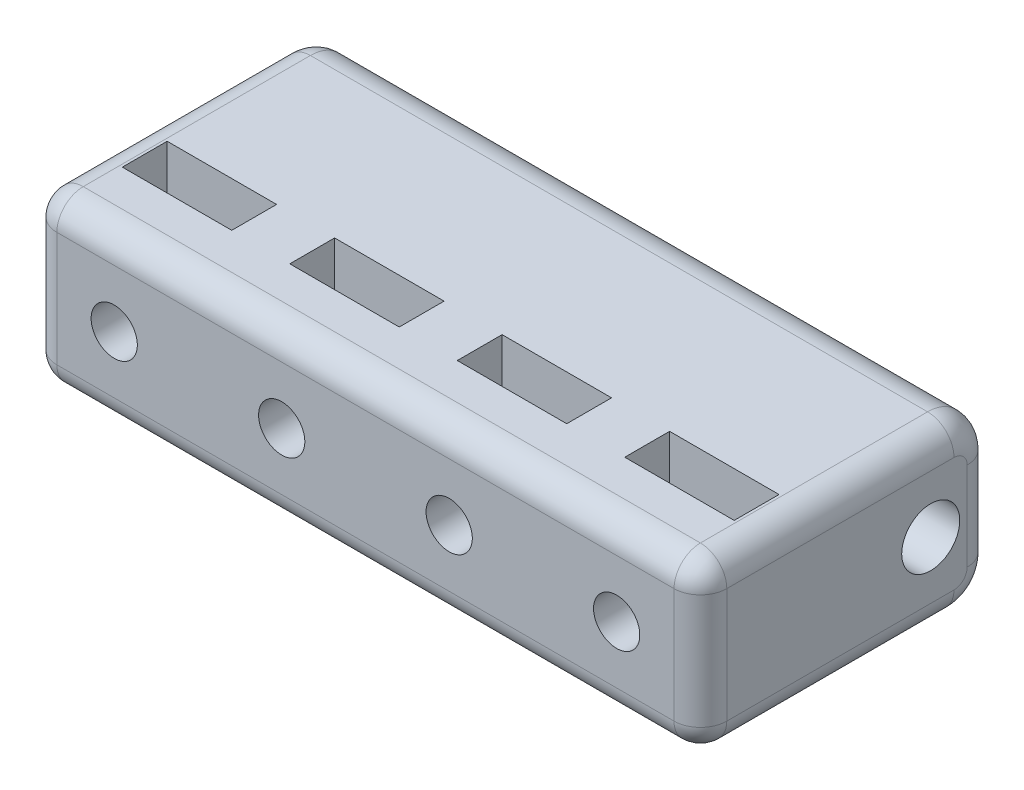
SolidWorks part; units mm, degrees
ref_plane "Front Plane" through (0, 0, 0) normal (0, 0, 1) x (1, 0, 0)
ref_plane "Top Plane" through (0, 0, 0) normal (0, 1, 0) x (1, 0, 0)
ref_plane "Right Plane" through (0, 0, 0) normal (1, 0, 0) x (0, 0, -1)
sketch "Sketch1" plane through (0, 0, 0) normal (0, 1, 0) x (1, 0, 0)
  line L1 (0, 0) -> (-50.8, 0)
  line L2 (0, 0) -> (0, -22.225)
  line L3 (0, -22.225) -> (-50.8, -22.225)
  line L4 (-50.8, 0) -> (-50.8, -22.225)
  dimension "D1" = 22.225
  dimension "D2" = 50.8
extrude "Boss-Extrude1" add sketch "Sketch1" along normal blind 12.7
sketch "Sketch2" plane through (-50.8, 0, 0) normal (-1, 0, 0) x (0, 0, 1)
  line L0 (0, 12.7) -> (0, 0) construction
  circle A0 centre (4.7625, 6.35) radius 2.2
  point P9 (0, 6.35)
  dimension "D1" = 4.4
  dimension "D2" = 4.7625
extrude "Cut-Extrude1" cut sketch "Sketch2" against normal through all
sketch "Sketch3" plane through (0, 12.7, 0) normal (0, 1, 0) x (1, 0, 0)
  line L0 (-50.8, -17.4625) -> (0, -17.4625) construction
  line L1 (-50.8, 0) -> (-50.8, -22.225) construction
  line L2 (0, -22.225) -> (0, 0) construction
  dimension "D1" = 17.4625
ref_plane "Plane1" through (0, 0, 17.4625) normal (0, 0, 1) x (1, 0, 0)
sketch "Sketch4" plane through (0, 0, 17.4625) normal (0, 0, 1) x (1, 0, 0)
  line L0 (-50.8, 12.7) -> (-50.8, 0) construction
  line L1 (-44.45, 1.558) -> (-40.3, 3.954)
  line L2 (-40.3, 3.954) -> (-40.3, 8.746)
  line L3 (-40.3, 8.746) -> (-44.45, 11.142)
  line L4 (-44.45, 11.142) -> (-48.6, 8.746)
  line L5 (-48.6, 8.746) -> (-48.6, 3.954)
  line L6 (-48.6, 3.954) -> (-44.45, 1.558)
  line L7 (-48.6, 8.746) -> (-48.6, 12.7)
  line L26 (-50.8, 12.7) -> (0, 12.7) construction
  line L27 (-48.6, 12.7) -> (-40.3, 12.7)
  line L28 (-40.3, 12.7) -> (-40.3, 8.746)
  line L29 (-35.9, 8.746) -> (-35.9, 12.7)
  line L30 (-35.9, 8.746) -> (-35.9, 3.954)
  line L31 (-35.9, 3.954) -> (-31.75, 1.558)
  line L32 (-31.75, 1.558) -> (-27.6, 3.954)
  line L33 (-27.6, 3.954) -> (-27.6, 8.746)
  line L34 (-27.6, 12.7) -> (-27.6, 8.746)
  line L35 (-35.9, 12.7) -> (-27.6, 12.7)
  line L36 (-23.2, 8.746) -> (-23.2, 12.7)
  line L37 (-23.2, 8.746) -> (-23.2, 3.954)
  line L38 (-23.2, 3.954) -> (-19.05, 1.558)
  line L39 (-19.05, 1.558) -> (-14.9, 3.954)
  line L40 (-14.9, 3.954) -> (-14.9, 8.746)
  line L41 (-14.9, 12.7) -> (-14.9, 8.746)
  line L42 (-23.2, 12.7) -> (-14.9, 12.7)
  line L43 (-10.5, 8.746) -> (-10.5, 12.7)
  line L44 (-10.5, 8.746) -> (-10.5, 3.954)
  line L45 (-10.5, 3.954) -> (-6.35, 1.558)
  line L46 (-6.35, 1.558) -> (-2.2, 3.954)
  line L47 (-2.2, 3.954) -> (-2.2, 8.746)
  line L48 (-2.2, 12.7) -> (-2.2, 8.746)
  line L49 (-10.5, 12.7) -> (-2.2, 12.7)
  line L50 (-44.45, 6.35) -> (-31.75, 6.35) construction
  circle A0 centre (-44.45, 6.35) radius 4.15 construction
  circle A1 centre (-44.45, 6.35) radius 1.7525
  circle A2 centre (-31.75, 6.35) radius 1.7525
  circle A3 centre (-19.05, 6.35) radius 1.7525
  circle A4 centre (-6.35, 6.35) radius 1.7525
  point P11 (-50.8, 6.35)
  dimension "D2" = 8.3
  dimension "D3" = 3.505
  dimension "D1" = 6.35
  dimension "D4" = 4
  dimension "D5" = 12.7
extrude "Cut-Extrude3" cut sketch "Sketch4" against normal blind 3.4 contours L28 L27 L7 L4 L3 | L5 L6 L1 L2 L3 L4 A1 | L35 L29 L30 L31 L32 L33 L34 A2 | A2 | A1 | A3 | L42 L36 L37 L38 L39 L40 L41 A3 | L49 L43 L44 L45 L46 L47 L48 A4 | A4 region at (-46.4616, 2.8658, 17.4625) region at (-44.45, 11.2352, 17.4625) region at (-35.7611, 10.723, 17.4625) region at (-23.0611, 10.723, 17.4625) region at (-10.3611, 10.723, 17.4625) region at (-44.45, 6.35, 17.4625) region at (-31.75, 6.35, 17.4625) region at (-19.05, 6.35, 17.4625) region at (-6.35, 6.35, 17.4625)
extrude "Cut-Extrude4" cut sketch "Sketch4<3>" against normal blind 1 from surface contours A1 | A2 | A3 | A4 region at (-44.45, 6.35, 17.4625) region at (-31.75, 6.35, 17.4625) region at (-19.05, 6.35, 17.4625) region at (-6.35, 6.35, 17.4625) starting at face at (-44.45, 6.9732, 14.0625)
sketch "Sketch4<3>" plane through (0, 0, 17.4625) normal (0, 0, 1) x (1, 0, 0) same geometry as "Sketch4"
extrude "Cut-Extrude5" cut sketch "Sketch4<4>" along normal up to next contours A1 | A2 | A3 | A4 region at (-44.45, 6.35, 17.4625) region at (-31.75, 6.35, 17.4625) region at (-19.05, 6.35, 17.4625) region at (-6.35, 6.35, 17.4625)
sketch "Sketch4<4>" plane through (0, 0, 17.4625) normal (0, 0, 1) x (1, 0, 0) same geometry as "Sketch4"
fillet "Fillet1" radius 3 2 edges at (-25.4, 0, 0) (-25.4, 12.7, 0)
fillet "Fillet2" radius 2 2 edges at (-25.4, 0, 22.225) (-25.4, 12.7, 22.225)
fillet "Fillet3" radius 2 16 edges at (0, 12.1142, 21.6392) (0, 6.35, 22.225) (0, 0.5858, 21.6392) (0, 0, 11.6125) (0, 0.8787, 0.8787) (0, 11.8213, 0.8787) (-50.8, 11.8213, 0.8787) (-50.8, 0.8787, 0.8787) (-50.8, 0, 11.6125) (-50.8, 0.5858, 21.6392) (-50.8, 6.35, 22.225) (-50.8, 12.1142, 21.6392) (0, 12.7, 11.6125) (-50.8, 12.7, 11.6125) (0, 6.35, 0) (-50.8, 6.35, 0)
